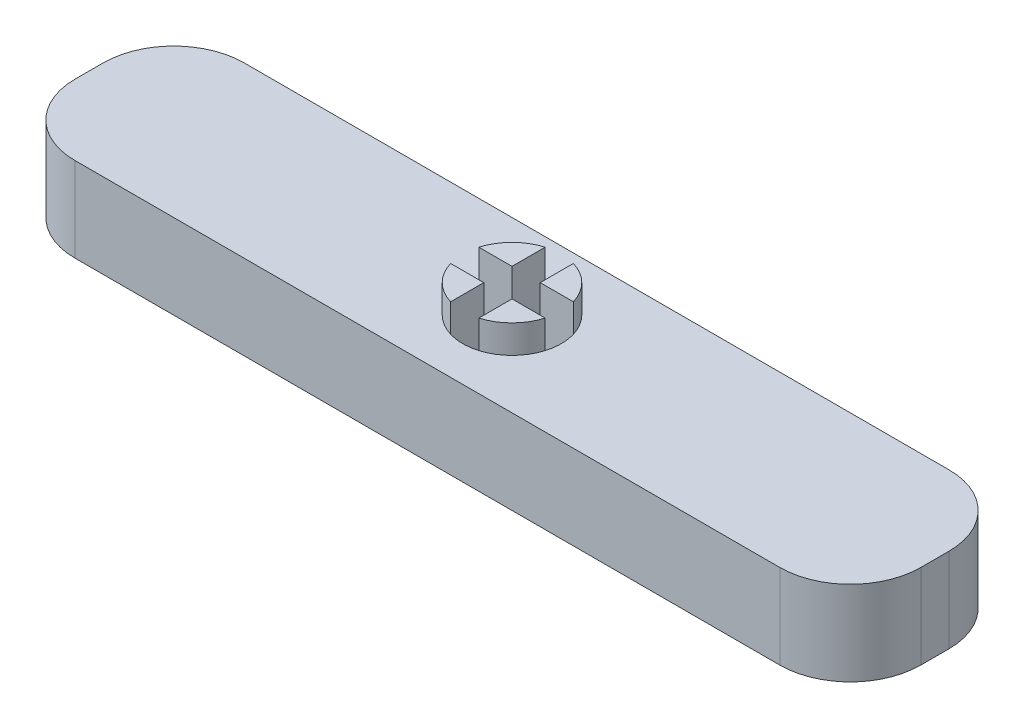
SolidWorks part; units mm, degrees
ref_plane "Płaszczyzna przednia" through (0, 0, 0) normal (0, 0, 1) x (1, 0, 0)
ref_plane "Płaszczyzna górna" through (0, 0, 0) normal (0, 1, 0) x (1, 0, 0)
ref_plane "Płaszczyzna prawa" through (0, 0, 0) normal (1, 0, 0) x (0, 0, -1)
sketch "Sketch1" plane through (0, 0, 0) normal (0, 1, 0) x (1, 0, 0)
  line L1 (-25, -6) -> (25, -6)
  line L2 (-30, -1) -> (-30, 1)
  line L3 (-25, 6) -> (25, 6)
  line L4 (30, -1) -> (30, 1)
  line L5 (-30, -6) -> (30, 6) construction
  line L6 (-30, 6) -> (30, -6) construction
  arc A0 (25, 6) -> (30, 1) centre (25, 1) cw
  arc A1 (25, -6) -> (30, -1) centre (25, -1) ccw
  arc A2 (-25, -6) -> (-30, -1) centre (-25, -1) cw
  arc A3 (-30, 1) -> (-25, 6) centre (-25, 1) cw
  point P0 (0, 0)
  dimension "D3" = 5
  dimension "D1" = 60
  dimension "D2" = 12
extrude "Boss-Extrude1" add sketch "Sketch1" along normal blind 6
sketch "Sketch2" plane through (0, 6, 0) normal (0, 1, 0) x (1, 0, 0)
  circle A0 centre (0, 0) radius 3.5
extrude "Boss-Extrude2" add sketch "Sketch2" along normal blind 2
sketch "Sketch3" plane through (0, 8, 0) normal (0, 1, 0) x (1, 0, 0)
  line L0 (-3.5, 0) -> (3.5, 0) construction
  line L1 (0, 2.7119) -> (1, 2.7119) construction
  line L2 (0, 3.5) -> (0, -3.5) construction
  line L3 (0, 2.7119) -> (-1, 2.7119) construction
  line L4 (2.9004, 0) -> (2.9004, 1) construction
  line L5 (2.9004, 0) -> (2.9004, -1) construction
  line L6 (1, 2.7119) -> (1, 3.3541)
  line L7 (1, 3.3541) -> (1, 1)
  line L8 (-1, 2.7119) -> (-1, 3.3541)
  line L9 (-1, 3.3541) -> (-1, 1)
  line L10 (2.9004, 1) -> (3.3541, 1)
  line L11 (3.3541, 1) -> (1, 1)
  line L12 (2.9004, -1) -> (3.3541, -1)
  line L13 (3.3541, -1) -> (1, -1)
  line L14 (-1, 1) -> (-3.3541, 1)
  line L15 (-1, -1) -> (-1, -3.3541)
  line L16 (1, -1) -> (1, -3.3541)
  line L17 (-1, -1) -> (-3.3541, -1)
  circle A0 centre (0, 0) radius 3.5 construction
  circle A1 centre (0, 0) radius 3.5 construction
  arc A2 (-3.3541, 1) -> (-3.3541, -1) centre (0, 0) ccw
  arc A3 (1, 3.3541) -> (-1, 3.3541) centre (0, 0) ccw
  arc A4 (3.3541, -1) -> (3.3541, 1) centre (0, 0) ccw
  arc A5 (-1, -3.3541) -> (1, -3.3541) centre (0, 0) ccw
  circle M6 centre (0, 0) radius 3.5
extrude "Cut-Extrude1" cut sketch "Sketch3" against normal blind 5 contours L17 L15 L16 L13 L12 L10 L11 L7 L6 L8 L9 L14 M6 region at (0, 8, 0)
